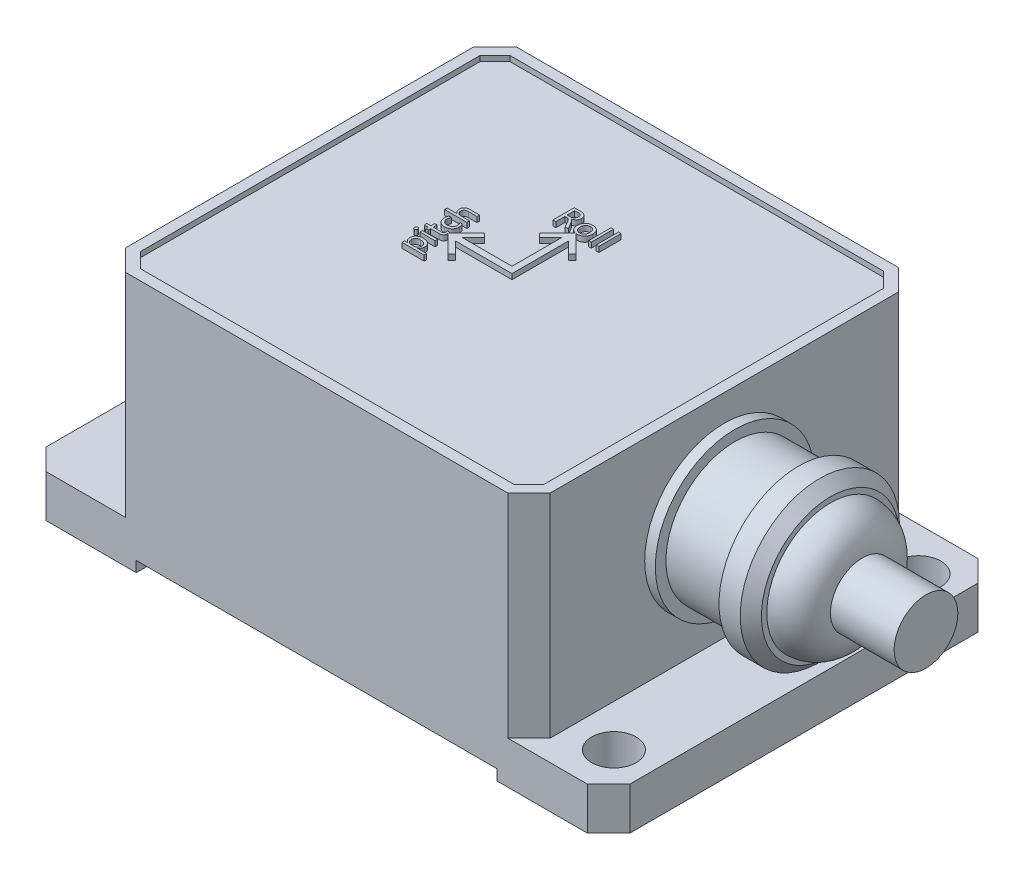
SolidWorks part; units mm, degrees
ref_plane "前视基准面" through (0, 0, 0) normal (0, 0, 1) x (1, 0, 0)
ref_plane "上视基准面" through (0, 0, 0) normal (0, 1, 0) x (1, 0, 0)
ref_plane "右视基准面" through (0, 0, 0) normal (1, 0, 0) x (0, 0, -1)
sketch "草图1" plane through (0, 0, 0) normal (0, 1, 0) x (1, 0, 0)
  line L1 (-27.5, 18.4) -> (27.5, 18.4)
  line L2 (-27.5, 18.4) -> (-27.5, -18.4)
  line L3 (-27.5, -18.4) -> (27.5, -18.4)
  line L4 (27.5, 18.4) -> (27.5, -18.4)
  line L5 (-27.5, 18.4) -> (27.5, -18.4) construction
  line L6 (-27.5, -18.4) -> (27.5, 18.4) construction
  point P0 (0, 0)
  dimension "D1" = 55
  dimension "D2" = 36.8
extrude "凸台-拉伸1" add sketch "草图1" along normal blind 4
sketch "草图2" plane through (0, 4, 0) normal (0, 1, 0) x (1, 0, 0)
  line L0 (27.5, 18.4) -> (-27.5, 18.4) construction
  line L1 (-20, -18.4) -> (20, -18.4)
  line L2 (-20, -18.4) -> (-20, 18.4)
  line L3 (-20, 18.4) -> (20, 18.4)
  line L4 (20, -18.4) -> (20, 18.4)
  line L5 (-20, -18.4) -> (20, 18.4) construction
  line L6 (-20, 18.4) -> (20, -18.4) construction
  point P0 (0, 0)
  dimension "D1" = 40
extrude "凸台-拉伸2" add sketch "草图2" along normal blind 20
chamfer "倒角1" distance 2 angle 45 8 edges at (-27.5, 2, 18.4) (-27.5, 2, -18.4) (27.5, 2, -18.4) (20, 14, -18.4) (20, 14, 18.4) (27.5, 2, 18.4) (-20, 14, -18.4) (-20, 14, 18.4)
sketch "草图3" plane through (0, 4, 0) normal (0, 1, 0) x (1, 0, 0)
  line L0 (-27.5, 0) -> (27.5, 0) construction
  line L1 (-27.5, 16.4) -> (-27.5, -16.4) construction
  line L2 (27.5, -16.4) -> (27.5, 16.4) construction
  line L3 (0, 18.4) -> (0, -18.4) construction
  line L4 (18, 18.4) -> (-18, 18.4) construction
  line L5 (-18, -18.4) -> (18, -18.4) construction
  circle A0 centre (-23.95, 0) radius 2.1
  circle A1 centre (23.95, -14.35) radius 2.1
  circle A2 centre (23.95, 14.35) radius 2.1
  dimension "D1" = 4.2
  dimension "D2" = 4.2
  dimension "D3" = 28.7
  dimension "D4" = 23.95
  dimension "D5" = 23.95
extrude "切除-拉伸1" cut sketch "草图3" against normal blind 20
sketch "草图4" plane through (0, 0, 18.4) normal (0, 0, 1) x (1, 0, 0)
  line L0 (18, 4) -> (18, 24) construction
  line L1 (-17, -1) -> (17, -1)
  line L2 (-17, -1) -> (-17, 1)
  line L3 (-17, 1) -> (17, 1)
  line L4 (17, -1) -> (17, 1)
  line L5 (-17, -1) -> (17, 1) construction
  line L6 (-17, 1) -> (17, -1) construction
  point P0 (0, 0)
  dimension "D1" = 2
  dimension "D2" = 1
extrude "切除-拉伸2" cut sketch "草图4" against normal through all
sketch "草图5" plane through (0, 24, 0) normal (0, 1, 0) x (1, 0, 0)
  line L16 (17.5858, 17.4) -> (-17.5858, 17.4)
  line L17 (-17.5858, 17.4) -> (-19, 15.9858)
  line L18 (-19, 15.9858) -> (-19, -15.9858)
  line L19 (-19, -15.9858) -> (-17.5858, -17.4)
  line L20 (-17.5858, -17.4) -> (17.5858, -17.4)
  line L21 (17.5858, -17.4) -> (19, -15.9858)
  line L22 (19, -15.9858) -> (19, 15.9858)
  line L23 (19, 15.9858) -> (17.5858, 17.4)
  line L24 (17.5858, 17.4) -> (-17.5858, 17.4)
  line L25 (-17.5858, 17.4) -> (-19, 15.9858)
  line L26 (-19, 15.9858) -> (-19, -15.9858)
  line L27 (-19, -15.9858) -> (-17.5858, -17.4)
  line L28 (-17.5858, -17.4) -> (17.5858, -17.4)
  line L29 (17.5858, -17.4) -> (19, -15.9858)
  line L30 (19, -15.9858) -> (19, 15.9858)
  line L31 (19, 15.9858) -> (17.5858, 17.4)
  dimension "D1" = 1
extrude "切除-拉伸3" cut sketch "草图5" against normal blind 0.5
sketch "草图6" plane through (0, 23.5, 0) normal (0, 1, 0) x (1, 0, 0)
  line L0 (0, 0) -> (-5, 0) construction
  line L1 (-0.3, 0.3) -> (-5, 0.3)
  line L2 (0, -0.3) -> (-5, -0.3)
  line L3 (-5, -0.3) -> (-3.9393, -1.3607)
  line L4 (-3.9393, -1.3607) -> (-4.2929, -1.7142)
  line L5 (-4.2929, -1.7142) -> (-6.0071, 0)
  line L6 (-5, 0) -> (-6.836, 0) construction
  line L7 (-4.2929, 1.7142) -> (-6.0071, 0)
  line L8 (-3.9393, 1.3607) -> (-4.2929, 1.7142)
  line L9 (-5, 0.3) -> (-3.9393, 1.3607)
  line L10 (0.3, 0) -> (0.3, 5)
  line L11 (-0.3, 0.3) -> (-0.3, 5)
  line L12 (-0.3, 5) -> (-1.3607, 3.9393)
  line L13 (-1.3607, 3.9393) -> (-1.7142, 4.2929)
  line L14 (-1.7142, 4.2929) -> (0, 6.0071)
  line L15 (1.7142, 4.2929) -> (0, 6.0071)
  line L16 (1.3607, 3.9393) -> (1.7142, 4.2929)
  line L17 (0.3, 5) -> (1.3607, 3.9393)
  line L18 (0, 0.3) -> (0, 5) construction
  line L19 (0, 5) -> (0, 6.836) construction
  line L20 (0, 0) -> (0, 0.3) construction
  line L21 (0, 0) -> (0.3, 0) construction
  line L22 (0, -0.3) -> (0.3, -0.3)
  line L23 (0.3, -0.3) -> (0.3, 0)
  line L25 (0, 0.3) -> (-5, 0.3) construction
  dimension "D1" = 5
  dimension "D4" = 0.5
  dimension "D5" = 45
  dimension "D6" = 1.5
  dimension "D7" = 90
  dimension "D2" = 2
  dimension "D3" = 0.3
extrude "凸台-拉伸3" add sketch "草图6" along normal blind 0.5
sketch "草图7" plane through (0, 23.5, 0) normal (0, 1, 0) x (1, 0, 0)
  line L0 (-6.0071, -4) -> (-6.0071, 4) construction
  line L2 (-4, 6.0071) -> (4, 6.0071) construction
  text T0 "pitch" font "微软雅黑" height 2
  text T1 "Roll" font "微软雅黑" height 2
  point P5 (-6.0071, 0)
  point P8 (0, 6.0071)
  dimension "D1" = 8
  dimension "D2" = 8
extrude "凸台-拉伸4" add sketch "草图7" along normal blind 0.5
sketch "草图9" plane through (20, 0, 0) normal (1, 0, 0) x (0, 0, -1)
  line L0 (0, 24) -> (0, 4) construction
  line L1 (-16.4, 24) -> (16.4, 24) construction
  line L2 (-16.4, 4) -> (16.4, 4) construction
  circle A0 centre (0, 14) radius 7.5
  dimension "D1" = 15
extrude "凸台-拉伸5" add sketch "草图9" along normal blind 10
sketch "草图10" plane through (30, 0, 0) normal (1, 0, 0) x (0, 0, -1)
  circle A0 centre (0, 14) radius 6
  dimension "D1" = 12
extrude "凸台-拉伸6" add sketch "草图10" along normal blind 3
fillet "圆角1" radius 3 1 edges at (33, 14, -6)
sketch "草图11" plane through (33, 0, 0) normal (1, 0, 0) x (0, 0, -1)
  circle A1 centre (0, 14) radius 3
  circle A2 centre (0, 14) radius 3
  dimension "D1" = 0
extrude "凸台-拉伸7" add sketch "草图11" along normal blind 6
chamfer "倒角2" distance 1 angle 45 1 edges at (30, 14, -7.5)
ref_plane "基准面1" through (21, 0, 0) normal (1, 0, 0) x (0, 0, -1)
sketch "草图12" plane through (21, 0, 0) normal (1, 0, 0) x (0, 0, -1)
  circle A0 centre (0, 14) radius 6.5
  circle A1 centre (0, 14) radius 7.5
extrude "切除-拉伸4" cut sketch "草图12" along normal blind 6
